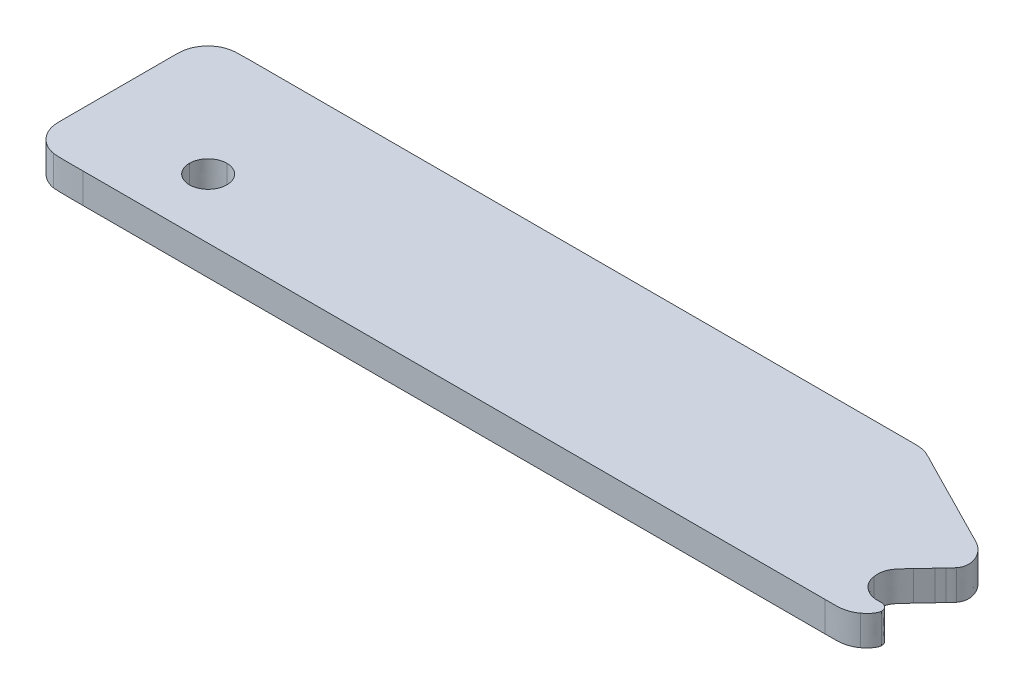
SolidWorks part; units mm, degrees
ref_plane "Front Plane" through (0, 0, 0) normal (0, 0, 1) x (1, 0, 0)
ref_plane "Top Plane" through (0, 0, 0) normal (0, 1, 0) x (1, 0, 0)
ref_plane "Right Plane" through (0, 0, 0) normal (1, 0, 0) x (0, 0, -1)
sketch "Sketch1" plane through (0, 0, 0) normal (0, 1, 0) x (1, 0, 0)
  spline S0 degree 3 poles (174.8406, 5.6295) (175.3918, 5.6272) (175.9155, 5.7307) (176.4598, 5.4343) knots 0 0 0 0 1 1 1 1
  spline S1 degree 3 poles (176.4598, 5.4343) (177.0317, 5.1242) (177.2659, 4.7453) (177.2866, 4.0906) knots 0 0 0 0 1 1 1 1
  spline S2 degree 3 poles (177.2866, 4.0906) (177.3141, 3.1261) (176.0809, 1.9478) (175.4538, 1.4862) knots 0 0 0 0 1 1 1 1
  spline S3 degree 3 poles (175.4538, 1.4862) (173.4075, -0.0297) (171.3542, 0.239) (169.1218, 0.239) knots 0 0 0 0 1 1 1 1
  spline S4 degree 3 poles (169.1218, 0.239) (164.7602, 0.239) (160.3988, 0.239) (156.0442, 0.239) knots 0 0 0 0 1 1 1 1
  spline S5 degree 3 poles (156.0442, 0.239) (147.3212, 0.239) (138.5982, 0.239) (129.8821, 0.239) knots 0 0 0 0 1 1 1 1
  spline S6 degree 3 poles (129.8821, 0.239) (112.3879, 0.239) (94.8937, 0.239) (77.3926, 0.239) knots 0 0 0 0 1 1 1 1
  spline S7 degree 3 poles (77.3926, 0.239) (59.8847, 0.239) (42.3836, 0.239) (24.8756, 0.239) knots 0 0 0 0 1 1 1 1
  spline S8 degree 3 poles (24.8756, 0.239) (20.5279, 0.239) (16.1802, 0.239) (11.8393, 0.239) knots 0 0 0 0 1 1 1 1
  spline S9 degree 3 poles (11.8393, 0.239) (11.0194, 0.239) (6.2101, 0.199) (5.3833, 0.3496) knots 0 0 0 0 1 1 1 1
  spline S10 degree 3 poles (5.3833, 0.3496) (3.0681, 0.7975) (1.194, 2.4786) (0.505, 4.7248) knots 0 0 0 0 1 1 1 1
  spline S11 degree 3 poles (0.505, 4.7248) (0.1812, 5.7859) (0.2225, 6.8332) (0.2225, 7.9081) knots 0 0 0 0 1 1 1 1
  spline S12 degree 3 poles (0.2225, 7.9081) (0.2225, 8.9898) (0.2225, 10.0785) (0.2225, 11.1603) knots 0 0 0 0 1 1 1 1
  spline S13 degree 3 poles (0.2225, 11.1603) (0.2225, 13.3375) (0.2225, 15.5079) (0.2225, 17.6784) knots 0 0 0 0 1 1 1 1
  spline S14 degree 3 poles (0.2225, 17.6784) (0.2225, 22.0261) (0.2225, 26.3738) (0.2225, 30.7215) knots 0 0 0 0 1 1 1 1
  spline S15 degree 3 poles (0.2225, 30.7215) (0.2225, 31.7964) (0.1949, 32.8437) (0.5326, 33.9047) knots 0 0 0 0 1 1 1 1
  spline S16 degree 3 poles (0.5326, 33.9047) (0.9115, 35.0692) (1.511, 35.958) (2.4411, 36.7642) knots 0 0 0 0 1 1 1 1
  spline S17 degree 3 poles (2.4411, 36.7642) (4.398, 38.4454) (6.4237, 38.2939) (8.6905, 38.2939) knots 0 0 0 0 1 1 1 1
  spline S18 degree 3 poles (8.6905, 38.2939) (13.0451, 38.2939) (17.3997, 38.2939) (21.7543, 38.2939) knots 0 0 0 0 1 1 1 1
  spline S19 degree 3 poles (21.7543, 38.2939) (30.4635, 38.2939) (39.1659, 38.2939) (47.8751, 38.2939) knots 0 0 0 0 1 1 1 1
  spline S20 degree 3 poles (47.8751, 38.2939) (65.3624, 38.2939) (82.8497, 38.2939) (100.337, 38.2939) knots 0 0 0 0 1 1 1 1
  spline S21 degree 3 poles (100.337, 38.2939) (109.0875, 38.2939) (117.8312, 38.2939) (126.5817, 38.2939) knots 0 0 0 0 1 1 1 1
  spline S22 degree 3 poles (126.5817, 38.2939) (130.957, 38.2939) (135.3322, 38.2939) (139.7075, 38.2939) knots 0 0 0 0 1 1 1 1
  spline S23 degree 3 poles (139.7075, 38.2939) (141.8917, 38.2939) (144.0828, 38.2939) (146.267, 38.2939) knots 0 0 0 0 1 1 1 1
  spline S24 degree 3 poles (146.267, 38.2939) (147.3625, 38.2939) (148.4581, 38.2939) (149.5536, 38.2939) knots 0 0 0 0 1 1 1 1
  spline S25 degree 3 poles (149.5536, 38.2939) (150.656, 38.2939) (151.7171, 38.2788) (152.7851, 37.8733) knots 0 0 0 0 1 1 1 1
  spline S26 degree 3 poles (152.7851, 37.8733) (153.8118, 37.4808) (154.7419, 36.9225) (155.7065, 36.4264) knots 0 0 0 0 1 1 1 1
  spline S27 degree 3 poles (155.7065, 36.4264) (156.6781, 35.9304) (157.6427, 35.4412) (158.6142, 34.945) knots 0 0 0 0 1 1 1 1
  spline S28 degree 3 poles (158.6142, 34.945) (160.5504, 33.9597) (162.4865, 32.9744) (164.4226, 31.9891) knots 0 0 0 0 1 1 1 1
  spline S29 degree 3 poles (164.4226, 31.9891) (166.3588, 30.9969) (168.2949, 30.0116) (170.2311, 29.0263) knots 0 0 0 0 1 1 1 1
  spline S30 degree 3 poles (170.2311, 29.0263) (171.1957, 28.5303) (172.1672, 28.0411) (173.1318, 27.545) knots 0 0 0 0 1 1 1 1
  spline S31 degree 3 poles (173.1318, 27.545) (174.1034, 27.0555) (175.0887, 26.6354) (175.9224, 25.8845) knots 0 0 0 0 1 1 1 1
  spline S32 degree 3 poles (175.9224, 25.8845) (177.4176, 24.5408) (178.7405, 21.9364) (177.2866, 20.0209) knots 0 0 0 0 1 1 1 1
  spline S33 degree 3 poles (177.2866, 20.0209) (176.9559, 19.5869) (176.5632, 19.2147) (176.1911, 18.822) knots 0 0 0 0 1 1 1 1
  spline S34 degree 3 poles (176.1911, 18.822) (175.819, 18.4225) (175.4538, 18.0227) (175.0818, 17.63) knots 0 0 0 0 1 1 1 1
  spline S35 degree 3 poles (175.0818, 17.63) (174.3445, 16.8376) (173.6004, 16.0383) (172.8562, 15.246) knots 0 0 0 0 1 1 1 1
  spline S36 degree 3 poles (172.8562, 15.246) (171.3266, 13.5992) (169.7212, 12.3727) (170.1346, 9.658) knots 0 0 0 0 1 1 1 1
  spline S37 degree 3 poles (170.1346, 9.658) (170.3275, 8.4178) (170.8236, 7.5496) (171.7814, 6.7435) knots 0 0 0 0 1 1 1 1
  spline S38 degree 3 poles (171.7814, 6.7435) (172.2361, 6.3645) (172.7184, 6.0889) (173.2765, 5.896) knots 0 0 0 0 1 1 1 1
  spline S39 degree 3 poles (173.2765, 5.896) (173.5384, 5.8065) (173.8002, 5.7375) (174.0689, 5.6895) knots 0 0 0 0 1 1 1 1
  spline S40 degree 3 poles (174.0689, 5.6895) (174.1998, 5.6695) (174.3307, 5.6545) (174.4617, 5.6395) knots 0 0 0 0 1 1 1 1
  spline S41 degree 3 poles (174.4617, 5.6395) (174.5238, 5.6395) (174.5925, 5.6345) (174.6545, 5.6345) knots 0 0 0 0 1 1 1 1
  spline S42 degree 3 poles (174.6545, 5.6345) (174.6891, 5.6295) (174.7166, 5.6295) (174.7511, 5.6295) knots 0 0 0 0 1 1 1 1
  spline S43 degree 3 poles (174.7511, 5.6295) (174.7856, 5.6295) (174.9095, 5.6345) (174.8406, 5.6295) knots 0 0 0 0 1 1 1 1
  spline S44 degree 3 poles (29.5954, 12.9378) (29.5954, 10.7467) (27.8177, 8.969) (25.6266, 8.969) knots 0 0 0 0 1 1 1 1
  spline S45 degree 3 poles (25.6266, 8.969) (23.4355, 8.969) (21.6579, 10.7467) (21.6579, 12.9378) knots 0 0 0 0 1 1 1 1
  spline S46 degree 3 poles (21.6579, 12.9378) (21.6579, 15.1288) (23.4355, 16.9065) (25.6266, 16.9065) knots 0 0 0 0 1 1 1 1
  spline S47 degree 3 poles (25.6266, 16.9065) (27.8177, 16.9065) (29.5954, 15.1288) (29.5954, 12.9378) knots 0 0 0 0 1 1 1 1
extrude "Boss-Extrude1" add sketch "Sketch1" along normal blind 6.35
